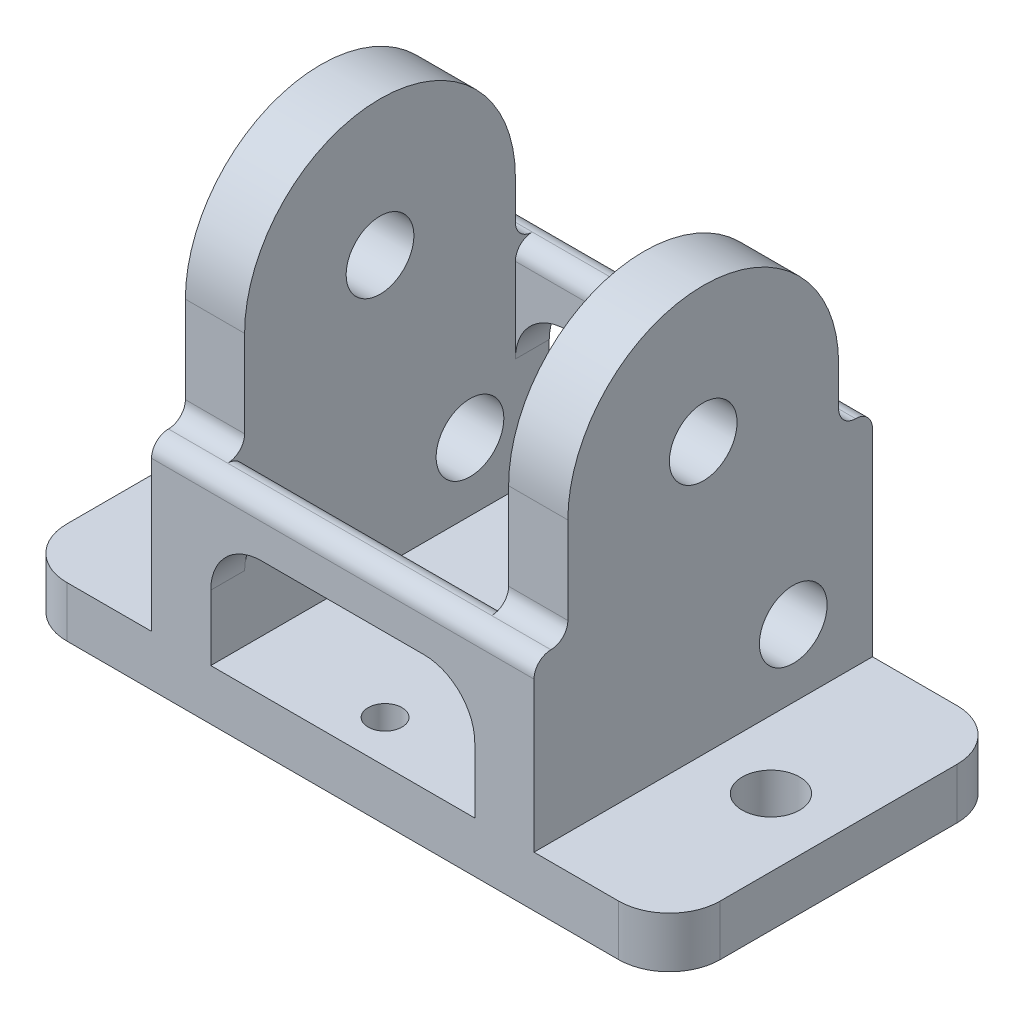
SolidWorks part; units mm, degrees
ref_plane "Plan de face" through (0, 0, 0) normal (0, 0, 1) x (1, 0, 0)
ref_plane "Plan de dessus" through (0, 0, 0) normal (0, 1, 0) x (1, 0, 0)
ref_plane "Plan de droite" through (0, 0, 0) normal (1, 0, 0) x (0, 0, -1)
sketch "Esquisse2" plane through (0, 0, 0) normal (0, 0, 1) x (1, 0, 0)
  line L0 (0, 1.475) -> (0, -1.8592) construction
  line L1 (-2.1467, 0) -> (3.7613, 0) construction
  line L4 (7.8, 2) -> (11.3, 2)
  line L5 (11.3, 2) -> (11.3, 8)
  line L6 (11.3, 8) -> (7.8, 8)
  line L7 (7.8, 8) -> (7.8, 2)
  dimension "D1" = 3.5
  dimension "D2" = 2
  dimension "D5" = 8
  dimension "D6" = 7.8
revolve "Révolution1" add sketch "Esquisse2" angle 360 about L1
sketch "Esquisse3" plane through (11.3, 0, 0) normal (1, 0, 0) x (0, 0, -1)
  line L1 (-10, -19) -> (10, -19)
  line L3 (-10, -16) -> (10, -16)
  line L4 (3.318, 0) -> (3.318, -16) construction
  line L5 (8, 0) -> (8, -6.3137)
  line L6 (5.6569, -5.6569) -> (12.7279, 1.4142) construction
  line L7 (0, -8) -> (10, -8) construction
  line L8 (8, -3.3137) -> (10, -3.3137)
  line L9 (10, -3.3137) -> (10, -19)
  line L10 (8, -6.3137) -> (10, -6.3137)
  line L11 (-5.6569, -5.6569) -> (-12.7279, 1.4142) construction
  line L12 (-8, -6.1421) -> (-10, -6.1421)
  line L13 (-12.7279, -1.4142) -> (-6.1421, -8) construction
  line L14 (-8, 0) -> (-8, -9.1421)
  line L15 (-8, -9.1421) -> (-10, -9.1421)
  line L16 (-10, -6.1421) -> (-10, -19)
  circle A0 centre (0, 0) radius 8 construction
  arc A1 (-8, 0) -> (8, 0) centre (0, 0) ccw
  circle A2 centre (0, 0) radius 3.318 construction
  circle A3 centre (5.318, -12) radius 2
  circle M5 centre (0, 0) radius 8
  dimension "D3" = 6.636
  dimension "D4" = 4
  dimension "D5" = 2
  dimension "D1" = 2
  dimension "D2" = 3
  dimension "D6" = 45
  dimension "D7" = 10
  dimension "D8" = 2
  dimension "D9" = 3
  dimension "D10" = 2
  dimension "D11" = 45
  dimension "D12" = 2
  dimension "D13" = 3
extrude "Boss.-Extru.1" add sketch "Esquisse3" against normal up to surface (3.5 mm away) contours L3 L1 | L3 M5 | L5 L10 L9 L8 | L12 L16 L15 L14 region at (11.3, -17.5, 0) region at (11.3, -11.0485, 0.0904) region at (11.3, -7.6421, 9) region at (11.3, -4.8137, -9) up to face at (7.8, 0, 2)
extrude "Boss.-Extru.2" add sketch "Esquisse3<3>" against normal up to surface (11.3 mm away) from surface contours L3 L1 | L5 L10 L9 L8 | L12 L16 L15 L14 region at (11.3, -17.5, 0) region at (11.3, -7.6421, 9) region at (11.3, -4.8137, -9) up to plane "Plan de droite" starting at face at (7.8, 0, 2)
sketch "Esquisse3<3>" plane through (11.3, 0, 0) normal (1, 0, 0) x (0, 0, -1) same geometry as "Esquisse3"
extrude "Boss-Extrude1" add sketch "Esquisse3<5>" along normal blind 8 contours L3 L16 L1 L9 region at (11.3, -17.5, 0)
sketch "Esquisse3<5>" plane through (11.3, 0, 0) normal (1, 0, 0) x (0, 0, -1) same geometry as "Esquisse3"
sketch "Sketch4" plane through (0, -16, 0) normal (0, 1, 0) x (1, 0, 0)
  line L0 (19.3, 10) -> (11.3, 10) construction
  circle A0 centre (15.3, 0) radius 1.7
  point P6 (15.3, 10)
  dimension "D1" = 3.4
extrude "Cut-Extrude1" cut sketch "Sketch4" against normal up to next
mirror "Symétrie1" about plane through (0, 0, 0) normal (1, 0, 0) of bodies 110 103
sketch "Sketch1" plane through (0, -16, 0) normal (0, 1, 0) x (1, 0, 0)
  point P3 (0, -7.5)
  dimension "D1" = 7.5
hole_wizard "Trous de centrage Ø2.0mm1" positions "Sketch1" profile "Sketch3" hole size "Ø2.0" standard "Ansi Metric" end condition up to next
sketch "Sketch3" plane through (0, -16, 7.5) normal (1, 0, 0) x (0, 0, 1)
  line L0 (0, 0) -> (0, 3)
  line L1 (0, 3) -> (1, 3)
  line L2 (1, 3) -> (1, 0)
  line L5 (1, 0) -> (0, 0)
  line L11 (0, -6.35) -> (0, 107.95) construction
  dimension "Thru Hole Dia." = 2
  dimension "Thru Hole Depth" = 3
fillet "Fillet1" radius 1 4 edges at (-9.55, -3.3137, -8) (9.55, -3.3137, -8) (-9.55, -6.1421, 8) (9.55, -6.1421, 8)
fillet "Fillet2" radius 1 4 edges at (0, -3.3137, -8) (0, -3.3137, -10) (0, -6.1421, 10) (0, -6.1421, 8)
fillet "Fillet3" radius 3 8 edges at (-7.8, -6.3137, -9) (7.8, -6.3137, -9) (7.8, -9.1421, 9) (-7.8, -9.1421, 9) (-19.3, -17.5, 10) (-19.3, -17.5, -10) (19.3, -17.5, -10) (19.3, -17.5, 10)
